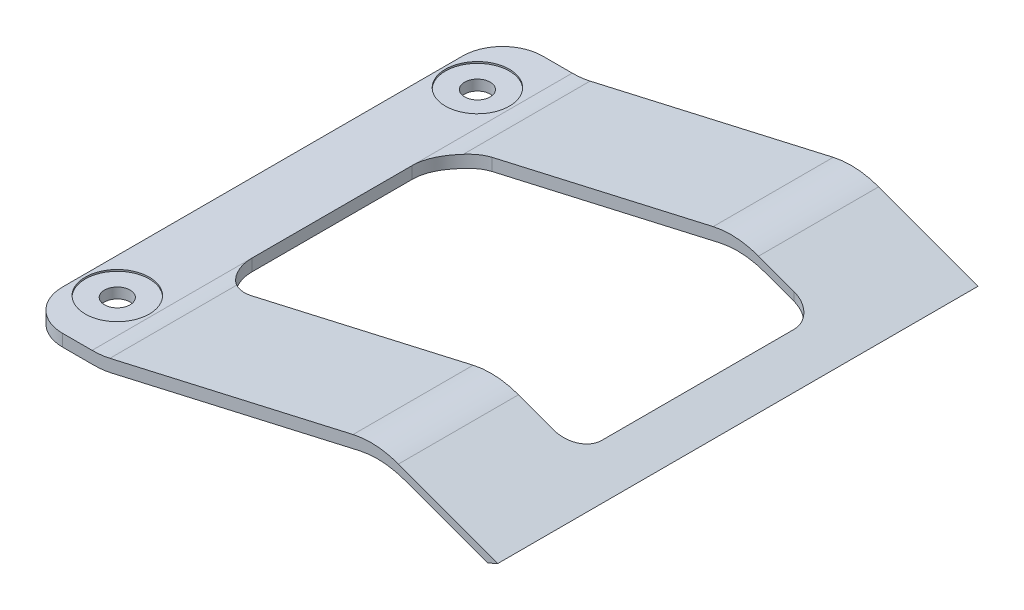
SolidWorks part; units mm, degrees
ref_plane "前视基准面" through (0, 0, 0) normal (0, 0, 1) x (1, 0, 0)
ref_plane "上视基准面" through (0, 0, 0) normal (0, 1, 0) x (1, 0, 0)
ref_plane "右视基准面" through (0, 0, 0) normal (1, 0, 0) x (0, 0, -1)
other "Configuration Table"
sketch "草图1" plane through (0, 0, 0) normal (0, 0, 1) x (1, 0, 0)
  line L0 (0, 0) -> (10, 0)
  line L1 (10, 0) -> (45, 8)
  line L2 (45, 8) -> (60, 2.5)
  line L3 (0, 0) -> (0, 1.5)
  line L4 (0, 1.5) -> (9.8308, 1.5)
  line L5 (9.8308, 1.5) -> (44.2044, 9.3568)
  line L6 (44.2044, 9.3568) -> (60, 3.5651)
  line L7 (60, 3.5651) -> (60, 2.5)
  dimension "D1" = 10
  dimension "D2" = 35
  dimension "D3" = 2.5
  dimension "D4" = 8
  dimension "D5" = 15
  dimension "D6" = 1.5
  dimension "D7" = 1.5
  dimension "D8" = 1
extrude "凸台-拉伸1" add sketch "草图1" along normal blind 60
fillet "圆角1" radius 10 4 edges at (44.2044, 9.3568, 30) (45, 8, 30) (10, 0, 30) (9.8308, 1.5, 30)
chamfer "倒角1" distance 2 angle 45 1 edges at (60, 2.5, 30)
sketch "草图2" plane through (0, 1.5, 0) normal (0, 1, 0) x (1, 0, 0)
  line L0 (4.3512, 0) -> (4.3512, -60) construction
  line L1 (8.7024, 0) -> (0, 0) construction
  line L2 (8.7024, -60) -> (0, -60) construction
  line L3 (4.3512, -30) -> (0, -30) construction
  line L4 (0, -60) -> (0, 0) construction
  circle A0 centre (4.3512, -7.5) radius 1.6
  circle A1 centre (4.3512, -52.5) radius 1.6
  dimension "D1" = 45
  dimension "D2" = 3.2
extrude "切除-拉伸1" cut sketch "草图2" against normal up to next
sketch "草图3" plane through (0, 1.5, 0) normal (0, 1, 0) x (1, 0, 0)
  circle A0 centre (4.3512, -7.5) radius 4
  circle A1 centre (4.3512, -52.5) radius 4
  dimension "D1" = 8
extrude "切除-拉伸2" cut sketch "草图3" against normal blind 0.2
sketch "草图4" plane through (0, 1.5, 0) normal (0, 1, 0) x (1, 0, 0)
  line L1 (54.4054, -15) -> (8.7024, -15)
  line L2 (54.4054, -15) -> (54.4054, -45)
  line L3 (54.4054, -45) -> (8.7024, -45)
  line L4 (8.7024, -15) -> (8.7024, -45)
  line L5 (8.7024, -60) -> (8.7024, 0) construction
  line L6 (0, -30) -> (54.4054, -30) construction
  line L7 (0, -60) -> (0, 0) construction
  line L8 (59.4054, -60) -> (59.4054, 0) construction
  point P4 (51.2845, -15)
  point P12 (0, 0)
  dimension "D1" = 30
  dimension "D2" = 5
extrude "切除-拉伸3" cut sketch "草图4" against normal up to next and the other way up to next
fillet "圆角2" radius 5 4 edges at (8.7024, 0.75, 15) (8.7024, 0.75, 45) (0, 0.75, 0) (0, 0.75, 60)
fillet "圆角3" radius 3 2 edges at (54.4054, 5.0839, 45) (54.4054, 5.0839, 15)
